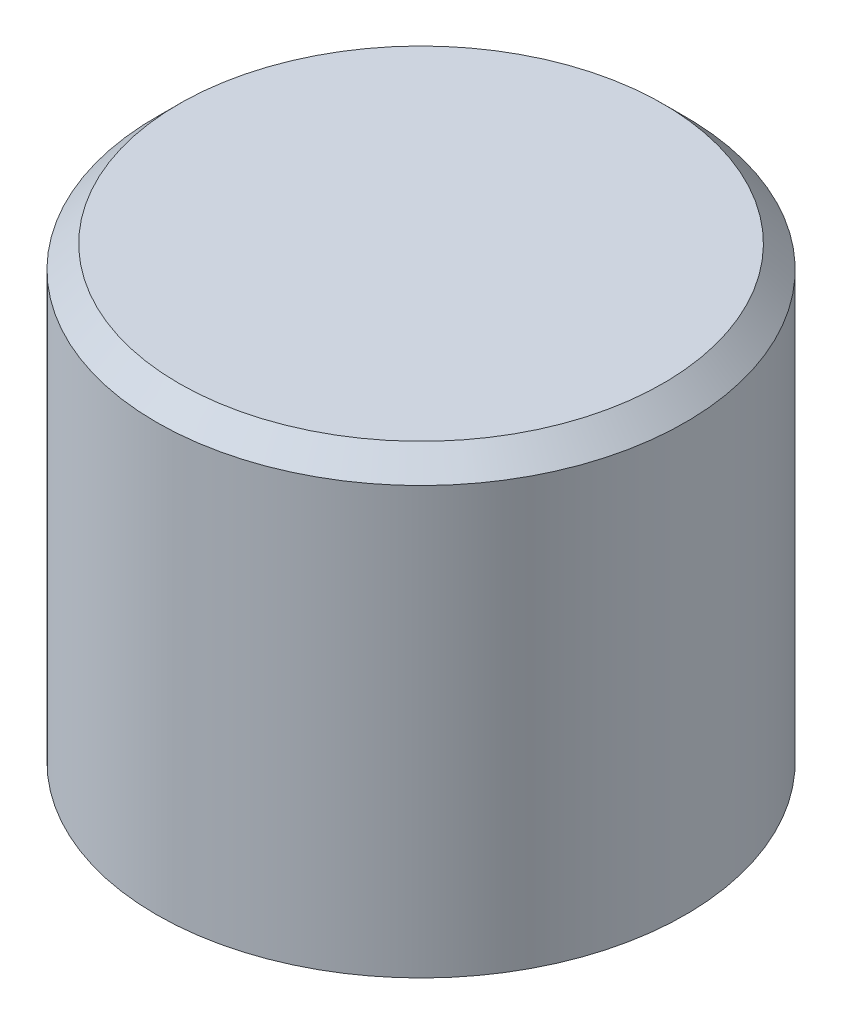
SolidWorks part; units mm, degrees
note: '?' marks a value the reader was unsure of.
material "3.3535 (EN-AW 5754)"
ref_plane "Ebene vorne" through (0, 0, 0) normal (0, 0, 1) x (1, 0, 0)
ref_plane "Ebene oben" through (0, 0, 0) normal (0, 1, 0) x (1, 0, 0)
ref_plane "Ebene rechts" through (0, 0, 0) normal (1, 0, 0) x (0, 0, -1)
ref_axis "Achse1" through (0, 0.7, 0) along (0, -1, 0)?
sketch "Skizze1" plane through (0, 0, 0) normal (0, 1, 0) x (1, 0, 0)
  circle A0 centre (0, 0) radius 8.25
  dimension "D1" = 16.5
extrude "Aufsatz-Linear austragen1" add sketch "Skizze1" along normal blind 14
chamfer "Fase1" distance 0.7 angle 45 1 edges at (0, 14, 8.25)
hole_wizard "Ø1.4 (1.4) Durchmesser Bohrung1" [suppressed] positions "Skizze3" profile "Skizze4" hole size "Ø1.4" standard "DIN"
sketch "Skizze3" plane through (0, 14, 0) normal (0, 1, 0) x (1, 0, 0)
  line L0 (0, 0) -> (0, 5.5) construction
  point P0 (0, 5.5)
  dimension "D1" = 5.5
sketch "Skizze4" plane through (0, 0, -5.5) normal (1, 0, 0) x (0, 0, 1)
  line L0 (0, 0) -> (0, 1.6206)
  line L1 (0, 1.6206) -> (0.7, 1.2)
  line L2 (0.7, 1.2) -> (0.7, 0)
  line L5 (0.7, 0) -> (0, 0)
  line L10 (0, 1.6206) -> (-0.7, 1.2) construction
  line L11 (0, -6.35) -> (0, 107.95) construction
  dimension "Bohrerdurchmesser" = 1.4
  dimension "Bohrungstiefe" = 1.2
  dimension "Spitzenwinkel" = 118
